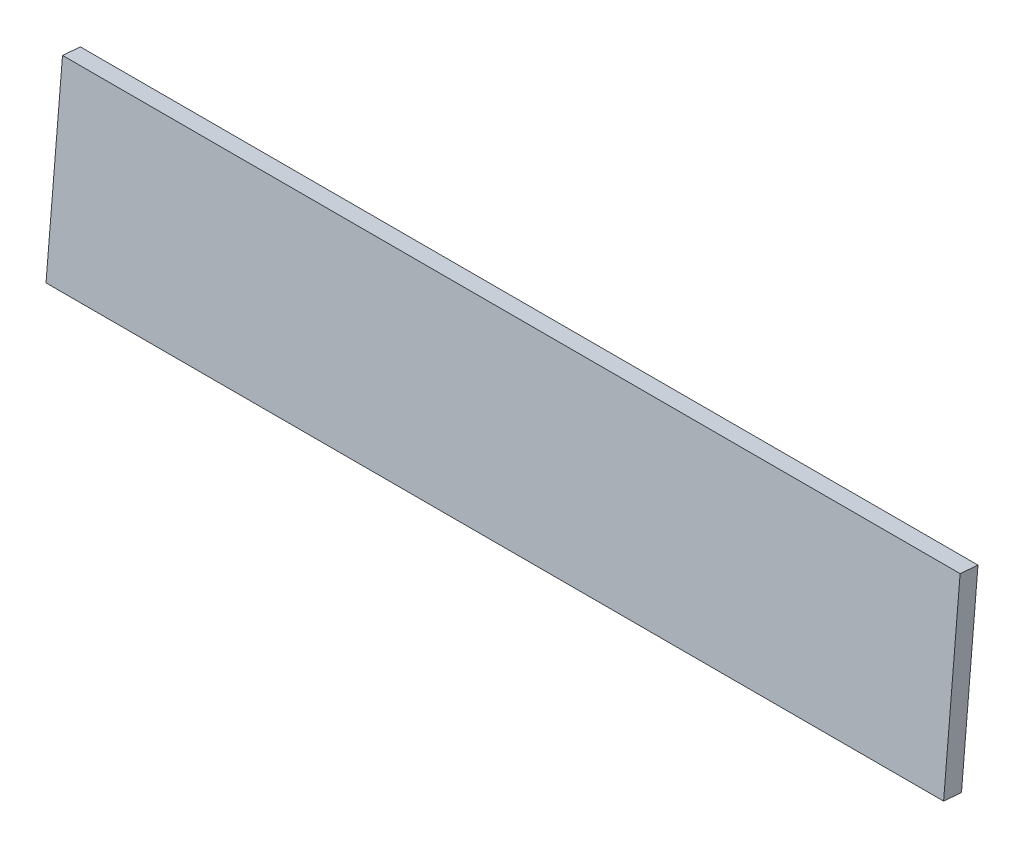
SolidWorks part; units mm, degrees
ref_plane "Front Plane" through (0, 0, 0) normal (0, 0, 1) x (1, 0, 0)
ref_plane "Top Plane" through (0, 0, 0) normal (0, 1, 0) x (1, 0, 0)
ref_plane "Right Plane" through (0, 0, 0) normal (1, 0, 0) x (0, 0, -1)
ref_axis "Pitch Axis" through (-88.99, 0, 0) along (1, 0, 0)
ref_plane "Basket Plane" through (0, 0, 0) normal (0, 0.0872, 0.9962) x (1, 0, 0)
sketch "Sketch1" plane through (0, 0, 0) normal (0, 0.0872, 0.9962) x (1, 0, 0)
  line L1 (-225, 95) -> (225, 95)
  line L2 (-225, 95) -> (-225, 0)
  line L3 (-225, 0) -> (225, 0)
  line L4 (225, 95) -> (225, 0)
  point P4 (0, 0)
  dimension "D1" = 95
  dimension "D2" = 450
extrude "Basket Wall" add sketch "Sketch1" along normal blind 9
